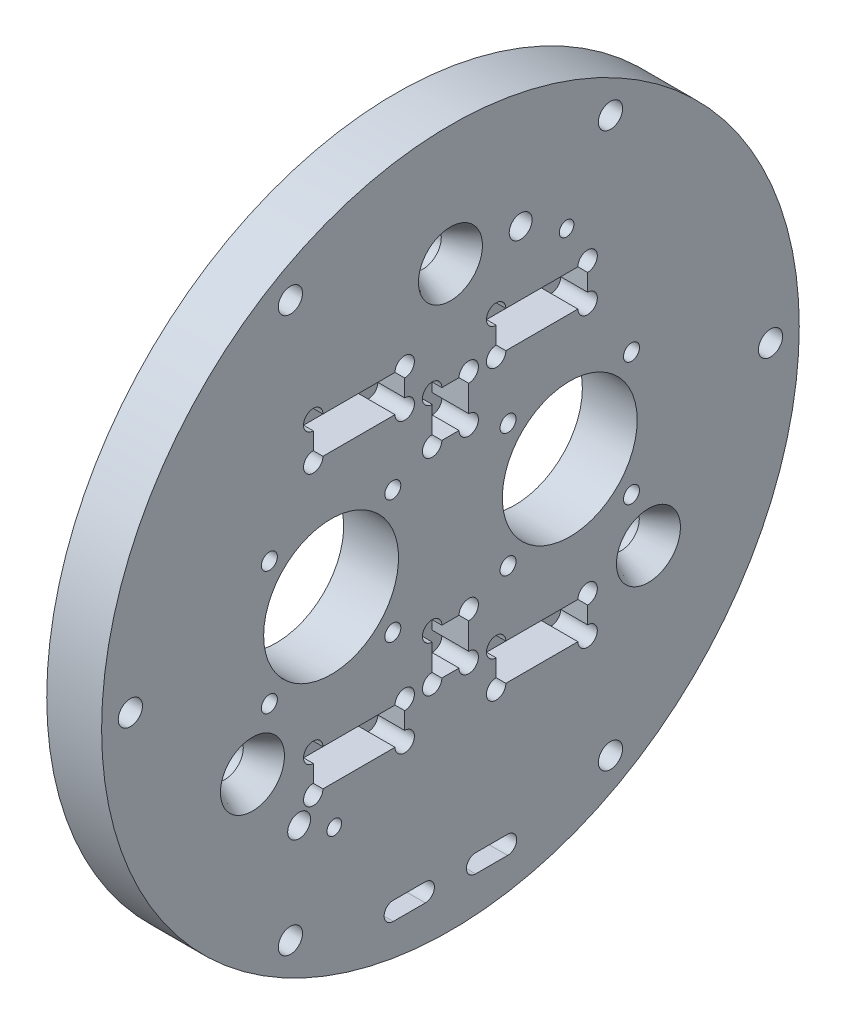
SolidWorks part; units mm, degrees
ref_plane "Front Plane" through (0, 0, 0) normal (0, 0, 1) x (1, 0, 0)
ref_plane "Top Plane" through (0, 0, 0) normal (0, 1, 0) x (1, 0, 0)
ref_plane "Right Plane" through (0, 0, 0) normal (1, 0, 0) x (0, 0, -1)
sketch "Sketch1" plane through (0, 0, 0) normal (1, 0, 0) x (0, 0, -1)
  line L0 (0, -76.29) -> (0, 76.29) construction
  line L1 (-76.29, 0) -> (76.29, 0) construction
  line L2 (26.1, 0) -> (39.5969, 13.4969) construction
  circle A0 centre (0, 0) radius 76.29
  circle A1 centre (0, 50) radius 4
  circle A2 centre (43.3013, -25) radius 4
  circle A3 centre (-43.3013, -25) radius 4
  circle A4 centre (26.1, 0) radius 14.75
  circle A5 centre (-26.1, 0) radius 14.75
  circle A6 centre (39.5969, 13.4969) radius 1.75
  circle A7 centre (39.5969, -13.4969) radius 1.75
  circle A8 centre (12.6031, -13.4969) radius 1.75
  circle A9 centre (12.6031, 13.4969) radius 1.75
  circle A10 centre (-39.5969, -13.4969) radius 1.75
  circle A11 centre (-12.6031, -13.4969) radius 1.75
  circle A12 centre (-12.6031, 13.4969) radius 1.75
  circle A13 centre (-39.5969, 13.4969) radius 1.75
  circle A14 centre (26.1, 0) radius 22.1 construction
  circle A15 centre (-26.1, 0) radius 22.1 construction
  point P12 (0, 0)
  point P29 (26.1, 0)
  point P37 (-4, 0)
  point P40 (4, 0)
  dimension "D1" = 152.58
  dimension "D2" = 8
  dimension "D5" = 29.5
  dimension "D7" = 3.5
  dimension "D11" = 44.2
  dimension "D3" = 50
  dimension "D4" = 3
  dimension "D6" = 8
  dimension "D8" = 19.0875
  dimension "D10" = 45
  dimension "D9" = 4
extrude "Boss-Extrude1" add sketch "Sketch1" along normal blind 12
sketch "Sketch2" plane through (12, 0, 0) normal (1, 0, 0) x (0, 0, -1)
  line L0 (-97.5918, 0) -> (102.3086, 0) construction
  line L1 (0, 96.3466) -> (0, -103.9448) construction
  line L2 (10, -27.5) -> (10, -35.5)
  line L3 (-30, -27.5) -> (-10, -27.5)
  line L4 (-30, -27.5) -> (-30, -35.5)
  line L5 (-30, -35.5) -> (-10, -35.5)
  line L6 (-10, -27.5) -> (-10, -35.5)
  line L7 (30, -27.5) -> (10, -27.5)
  line L8 (30, -27.5) -> (30, -35.5)
  line L9 (30, -35.5) -> (10, -35.5)
  line L10 (-30, 27.5) -> (-30, 35.5)
  line L11 (-30, 35.5) -> (-10, 35.5)
  line L12 (-10, 27.5) -> (-10, 35.5)
  line L13 (-30, 27.5) -> (-10, 27.5)
  line L14 (10, 27.5) -> (10, 35.5)
  line L15 (30, 35.5) -> (10, 35.5)
  line L16 (30, 27.5) -> (10, 27.5)
  line L17 (30, 27.5) -> (30, 35.5)
  line L18 (-4, -17.5) -> (4, -17.5)
  line L19 (-4, 27.5) -> (4, 27.5)
  line L20 (-4, 27.5) -> (-4, 17.5)
  line L21 (-4, 17.5) -> (4, 17.5)
  line L22 (4, 27.5) -> (4, 17.5)
  line L23 (-4, -27.5) -> (-4, -17.5)
  line L24 (-4, -27.5) -> (4, -27.5)
  line L25 (4, -27.5) -> (4, -17.5)
  line L26 (27.8787, -35.5) -> (30, -33.3787) construction
  line L27 (-42.3534, -68.29) -> (39.6493, -68.29) construction
  line L28 (-5.5, -68.29) -> (-5.5, -64.29)
  line L29 (12.5, -68.29) -> (5.5, -68.29)
  line L30 (12.5, -68.29) -> (12.5, -64.29)
  line L31 (12.5, -64.29) -> (5.5, -64.29)
  line L32 (5.5, -68.29) -> (5.5, -64.29)
  line L33 (-12.5, -64.29) -> (-5.5, -64.29)
  line L34 (-12.5, -68.29) -> (-12.5, -64.29)
  line L35 (-12.5, -68.29) -> (-5.5, -68.29)
  circle A0 centre (30, -35.5) radius 2.1213 construction
  circle A1 centre (0, 0) radius 76.29 construction
  point P23 (0, 27.5)
  point P31 (30, -33.3787)
  point P32 (0, -76.29)
  point P33 (27.8787, -35.5)
  dimension "D1" = 27.5
  dimension "D2" = 8
  dimension "D3" = 20
  dimension "D4" = 20
  dimension "D5" = 8
  dimension "D6" = 10
  dimension "D7" = 8
  dimension "D8" = 4
  dimension "D9" = 7
  dimension "D10" = 25
extrude "Cut-Extrude1" cut sketch "Sketch2" against normal blind 8
sketch "Sketch3" plane through (0, 0, 0) normal (-1, 0, 0) x (0, 0, 1)
  circle A0 centre (-70, 0) radius 2.65
  circle A1 centre (-35, 60.6218) radius 2.65
  circle A2 centre (35, 60.6218) radius 2.65
  circle A3 centre (70, 0) radius 2.65
  circle A4 centre (35, -60.6218) radius 2.65
  circle A5 centre (-35, -60.6218) radius 2.65
  point P16 (0, 0)
  dimension "D2" = 5.3
  dimension "D1" = 70
  dimension "D3" = 6
extrude "Cut-Extrude2" cut sketch "Sketch3" against normal up to next
sketch "Sketch4" plane through (12, 0, 0) normal (1, 0, 0) x (0, 0, -1)
  line L0 (12.5, -68.29) -> (12.5, -64.29) construction
  line L2 (5.5, -64.29) -> (5.5, -68.29) construction
  line L3 (-5.5, -68.29) -> (-5.5, -64.29) construction
  line L4 (-12.5, -64.29) -> (-12.5, -68.29) construction
  circle A0 centre (-10, -35.5) radius 2.1213
  circle A1 centre (-10, -27.5) radius 2.1213
  circle A2 centre (-30, -27.5) radius 2.1213
  circle A3 centre (-30, -35.5) radius 2.1213
  circle A4 centre (12.5, -66.29) radius 2
  circle A5 centre (5.5, -66.29) radius 2
  circle A6 centre (-5.5, -66.29) radius 2
  circle A7 centre (-12.5, -66.29) radius 2
  circle A12 centre (10, -35.5) radius 2.1213
  circle A13 centre (10, -27.5) radius 2.1213
  circle A14 centre (30, -27.5) radius 2.1213
  circle A15 centre (30, -35.5) radius 2.1213
  circle A16 centre (4, -27.5) radius 2.1213
  circle A17 centre (-4, -27.5) radius 2.1213
  circle A18 centre (-4, -17.5) radius 2.1213
  circle A19 centre (4, -17.5) radius 2.1213
  circle A20 centre (4, 27.5) radius 2.1213
  circle A21 centre (-4, 27.5) radius 2.1213
  circle A22 centre (-4, 17.5) radius 2.1213
  circle A23 centre (4, 17.5) radius 2.1213
  circle A24 centre (10, 27.5) radius 2.1213
  circle A25 centre (10, 35.5) radius 2.1213
  circle A26 centre (30, 35.5) radius 2.1213
  circle A27 centre (30, 27.5) radius 2.1213
  circle A28 centre (-10, 35.5) radius 2.1213
  circle A29 centre (-10, 27.5) radius 2.1213
  circle A30 centre (-30, 27.5) radius 2.1213
  circle A31 centre (-30, 35.5) radius 2.1213
  point P2 (-12.1213, -35.5)
  point P5 (-10, -33.3787)
  dimension "D1" = 3
extrude "Cut-Extrude3" cut sketch "Sketch4" against normal up to surface (8 mm away) up to face at (4, -31.5, 20)
sketch "Sketch5" plane through (0, 0, 0) normal (-1, 0, 0) x (0, 0, 1)
  line L0 (35, -60.6218) -> (-35, 60.6218) construction
  line L1 (0, 113.7201) -> (0, -122.5246) construction
  line L2 (-128.5049, 0) -> (121.7105, 0) construction
  circle A0 centre (35, -60.6218) radius 2.65 construction
  circle A1 centre (25.4034, -44) radius 1.6
  circle A2 centre (-25.4034, 44) radius 1.6
  point P12 (0, 0)
  dimension "D2" = 3.2
  dimension "D1" = 2
  dimension "D3" = 44
  dimension "D4" = 50.8068
extrude "Cut-Extrude4" cut sketch "Sketch5" against normal up to next
sketch "Sketch9" plane through (12, 0, 0) normal (1, 0, 0) x (0, 0, -1)
  circle A0 centre (0, 0) radius 51.7766 construction
  circle A1 centre (0, 51.7766) radius 15.533 construction
  circle A2 centre (15.3572, 49.4467) radius 2.5
  circle A4 centre (-33.0898, -39.8231) radius 2.5
  circle A5 centre (-43.3013, -25) radius 4 construction
  dimension "D1" = 5
  dimension "D2" = 5
  dimension "D3" = 18
extrude "Cut-Extrude6" cut sketch "Sketch9" against normal up to next
chamfer "Chamfer1" distance 3 distance2 6 3 edges at (12, 50, -4) (12, -25, -47.3013) (12, -25, 39.3013) first distance on face at (12, -39.8231, 30.5898)
